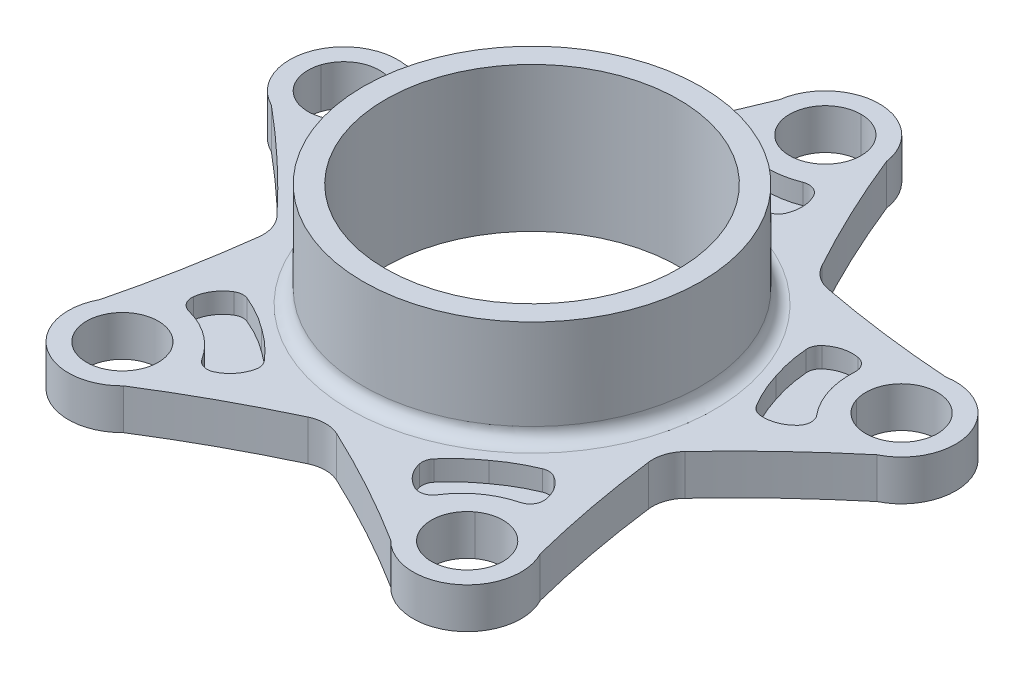
SolidWorks part; units mm, degrees
ref_plane "Front Plane" through (0, 0, 0) normal (0, 0, 1) x (1, 0, 0)
ref_plane "Top Plane" through (0, 0, 0) normal (0, 1, 0) x (1, 0, 0)
ref_plane "Right Plane" through (0, 0, 0) normal (1, 0, 0) x (0, 0, -1)
sketch "Sketch1" plane through (0, 0, 0) normal (0, 1, 0) x (1, 0, 0)
  circle A0 centre (0, 0) radius 31.75
  dimension "D1" = 63.5
extrude "CenterCircleExtrude" add sketch "Sketch1" along normal blind 19.558 contours A0
sketch "Sketch2" plane through (0, 0, 0) normal (0, -1, 0) x (1, 0, 0)
  circle A0 centre (0, 0) radius 80.01
  dimension "D1" = 160.02
extrude "BaseExpand" add sketch "Sketch2" along normal blind 7.62
sketch "Sketch3" plane through (0, 19.558, 0) normal (0, 1, 0) x (1, 0, 0)
  circle A0 centre (0, 0) radius 27.559
  dimension "D1" = 55.118
extrude "CenterCut" cut sketch "Sketch3" against normal blind 27.178 contours A0
sketch "Sketch4" plane through (0, 0, 0) normal (0, 1, 0) x (1, 0, 0)
  line L0 (-52.4203, 17.0324) -> (0, 55.118) construction
  line L1 (-26.2102, 36.0752) -> (-18.6622, 25.6863) construction
  circle A0 centre (0, 55.118) radius 6.731
  circle A1 centre (52.4203, 17.0324) radius 6.731
  circle A2 centre (32.3975, -44.5914) radius 6.731
  circle A3 centre (-32.3975, -44.5914) radius 6.731
  circle A4 centre (-52.4203, 17.0324) radius 6.731
  circle A5 centre (0, 0) radius 31.75 construction
  point P14 (0, 0)
  dimension "D1" = 13.462
  dimension "D2" = 55.118
  dimension "D3" = 5
extrude "OuterCircleCut" cut sketch "Sketch4" against normal blind 7.62
sketch "Sketch8" plane through (0, 0, 0) normal (0, 1, 0) x (1, 0, 0)
  line L0 (-52.4203, 17.0324) -> (0, 55.118) construction
  line L1 (-26.2102, 36.0752) -> (-18.6622, 25.6863) construction
  line L2 (26.2102, 36.0752) -> (18.6622, 25.6863) construction
  line L3 (42.4089, -13.7795) -> (30.196, -9.8113) construction
  line L4 (0, -44.5914) -> (0, -31.75) construction
  line L5 (-42.4089, -13.7795) -> (-30.196, -9.8113) construction
  line L6 (0, -14.9479) -> (0, 14.9479) construction
  line L8 (0, 0) -> (10.16, 55.118) construction
  line L9 (10.16, 55.118) -> (-10.16, 55.118) construction
  circle A0 centre (-52.4203, 17.0324) radius 10.16
  circle A1 centre (0, 55.118) radius 10.16
  circle A2 centre (52.4203, 17.0324) radius 10.16
  circle A3 centre (32.3975, -44.5914) radius 10.16
  circle A4 centre (-32.3975, -44.5914) radius 10.16
  circle A5 centre (0, 0) radius 31.75 construction
  arc A6 (22.4362, 30.8807) -> (8.4002, 60.8331) centre (204.9622, 134.6791) cw
  arc A7 (-22.4362, 30.8807) -> (-8.4002, 60.8331) centre (-204.9622, 134.6791) ccw
  arc A8 (22.4362, 30.8807) -> (55.2599, 26.7875) centre (64.7506, 236.5488) ccw
  arc A9 (36.3025, -11.7954) -> (60.4515, 10.8094) centre (191.4243, -153.3125) cw
  arc A10 (36.3025, -11.7954) -> (42.5527, -44.2774) centre (244.9803, 11.5161) ccw
  arc A11 (0, -38.1707) -> (28.9609, -54.1525) centre (-86.6555, -229.4315) cw
  arc A12 (0, -38.1707) -> (-28.9609, -54.1525) centre (86.6555, -229.4315) ccw
  arc A13 (-36.3025, -11.7954) -> (-42.5527, -44.2774) centre (-244.9803, 11.5161) cw
  arc A14 (-36.3025, -11.7954) -> (-60.4515, 10.8094) centre (-191.4243, -153.3125) ccw
  arc A15 (-22.4362, 30.8807) -> (-55.2599, 26.7875) centre (-64.7506, 236.5488) cw
  point P14 (0, 0)
  point P27 (0, 0)
  point P63 (0, 0)
  point P72 (0, 0)
  circle M12 centre (0, 0) radius 80.01
  dimension "D1" = 5
  dimension "D3" = 5
  dimension "D2" = 5
extrude "StarfishCut" cut sketch "Sketch8" against normal blind 7.62 contours A0 A1 A2 A3 A4 M12 region at (-77.747, 0, 0)
sketch "Sketch14" plane through (0, 0, 0) normal (0, 1, 0) x (1, 0, 0)
  line L4 (0, -14.9479) -> (0, 14.9479) construction
  arc A0 (38.2121, 3.6164) -> (34.5928, 11.2399) centre (62.2856, 19.7161) cw
  arc A1 (33.0399, 19.5348) -> (34.5928, 11.2399) centre (61.9789, 20.6599) ccw
  arc A2 (41.5686, 21.0847) -> (33.0399, 19.5348) centre (38.134, 15.7437) ccw
  arc A25 (7.2074, 46.0496) -> (-7.2074, 46.0496) centre (0, 59.4776) cw
  arc A26 (-7.2074, 46.0496) -> (-8.3688, 37.4594) centre (-3.1891, 41.1327) ccw
  arc A27 (-8.3688, 37.4594) -> (0, 36.3731) centre (-0.4961, 65.3297) ccw
  arc A45 (8.3688, 37.4594) -> (0, 36.3731) centre (0.4961, 65.3297) cw
  arc A46 (7.2074, 46.0496) -> (8.3688, 37.4594) centre (3.1891, 41.1327) cw
  arc A47 (46.023, 7.3755) -> (41.5686, 21.0847) centre (56.5665, 18.3796) cw
  arc A48 (46.023, 7.3755) -> (38.2121, 3.6164) centre (40.105, 9.6777) cw
  arc A49 (15.2476, -35.2243) -> (21.3796, -29.4264) centre (37.9984, -53.1445) cw
  arc A50 (28.7886, -25.3862) -> (21.3796, -29.4264) centre (38.8012, -52.5612) ccw
  arc A51 (32.8982, -33.0185) -> (28.7886, -25.3862) centre (26.7572, -31.4026) ccw
  arc A52 (21.2364, -41.4913) -> (32.8982, -33.0185) centre (34.96, -48.1184) cw
  arc A53 (21.2364, -41.4913) -> (15.2476, -35.2243) centre (21.5972, -35.1516) cw
  arc A54 (-28.7886, -25.3862) -> (-21.3796, -29.4264) centre (-38.8012, -52.5612) cw
  arc A55 (-15.2476, -35.2243) -> (-21.3796, -29.4264) centre (-37.9984, -53.1445) ccw
  arc A56 (-21.2364, -41.4913) -> (-15.2476, -35.2243) centre (-21.5972, -35.1516) ccw
  arc A57 (-32.8982, -33.0185) -> (-21.2364, -41.4913) centre (-34.96, -48.1184) cw
  arc A58 (-32.8982, -33.0185) -> (-28.7886, -25.3862) centre (-26.7572, -31.4026) cw
  arc A59 (-33.0399, 19.5348) -> (-34.5928, 11.2399) centre (-61.9789, 20.6599) cw
  arc A60 (-38.2121, 3.6164) -> (-34.5928, 11.2399) centre (-62.2856, 19.7161) ccw
  arc A61 (-46.023, 7.3755) -> (-38.2121, 3.6164) centre (-40.105, 9.6777) ccw
  arc A62 (-41.5686, 21.0847) -> (-46.023, 7.3755) centre (-56.5665, 18.3796) cw
  arc A63 (-41.5686, 21.0847) -> (-33.0399, 19.5348) centre (-38.134, 15.7437) cw
  point P34 (0, 0)
  point P51 (0, 0)
  point P61 (0, 0)
  point P97 (0, 0)
  dimension "D1" = 6.35
  dimension "D2" = 15.24
  dimension "D4" = 5
  dimension "D3" = 28.9609
extrude "Batman Cut" cut sketch "Sketch14" against normal blind 3.81
fillet "Fillet11" radius 2.54 20 edges at (21.2364, -1.905, 41.4913) (32.8982, -1.905, 33.0185) (28.7886, -1.905, 25.3862) (15.2476, -1.905, 35.2243) (-21.2364, -1.905, 41.4913) (-32.8982, -1.905, 33.0185) (-15.2476, -1.905, 35.2243) (-28.7886, -1.905, 25.3862) (-38.2121, -1.905, -3.6164) (-46.023, -1.905, -7.3755) (-33.0399, -1.905, -19.5348) (-41.5686, -1.905, -21.0847) (38.2121, -1.905, -3.6164) (33.0399, -1.905, -19.5348) (46.023, -1.905, -7.3755) (41.5686, -1.905, -21.0847) (-8.3688, -1.905, -37.4594) (8.3688, -1.905, -37.4594) (-7.2074, -1.905, -46.0496) (7.2074, -1.905, -46.0496)
ref_axis "Axis1" through (0, -7.62, 0) along (0, 1, 0)
fillet "Fillet12" radius 6.35 5 edges at (-36.3025, -3.81, 11.7954) (0, -3.81, 38.1707) (36.3025, -3.81, 11.7954) (22.4362, -3.81, -30.8807) (-22.4362, -3.81, -30.8807)
ref_plane "Plane1" through (0, 0, 0) normal (-0.309, 0, 0.9511) x (0.9511, 0, 0.309)
ref_plane "Plane2" through (0, 0, 0) normal (-0.809, 0, -0.5878) x (-0.5878, 0, 0.809)
ref_plane "Plane3" through (0, 0, 0) normal (-0.809, 0, 0.5878) x (0.5878, 0, 0.809)
ref_plane "Plane4" through (0, 0, 0) normal (0.309, 0, 0.9511) x (0.9511, 0, -0.309)
split line "Split Line1"
split line "Split Line2"
split line "Split Line3"
split line "Split Line4"
split line "Split Line5"
fillet "Fillet13" radius 2.54 1 edges at (0, 0, 31.75)
